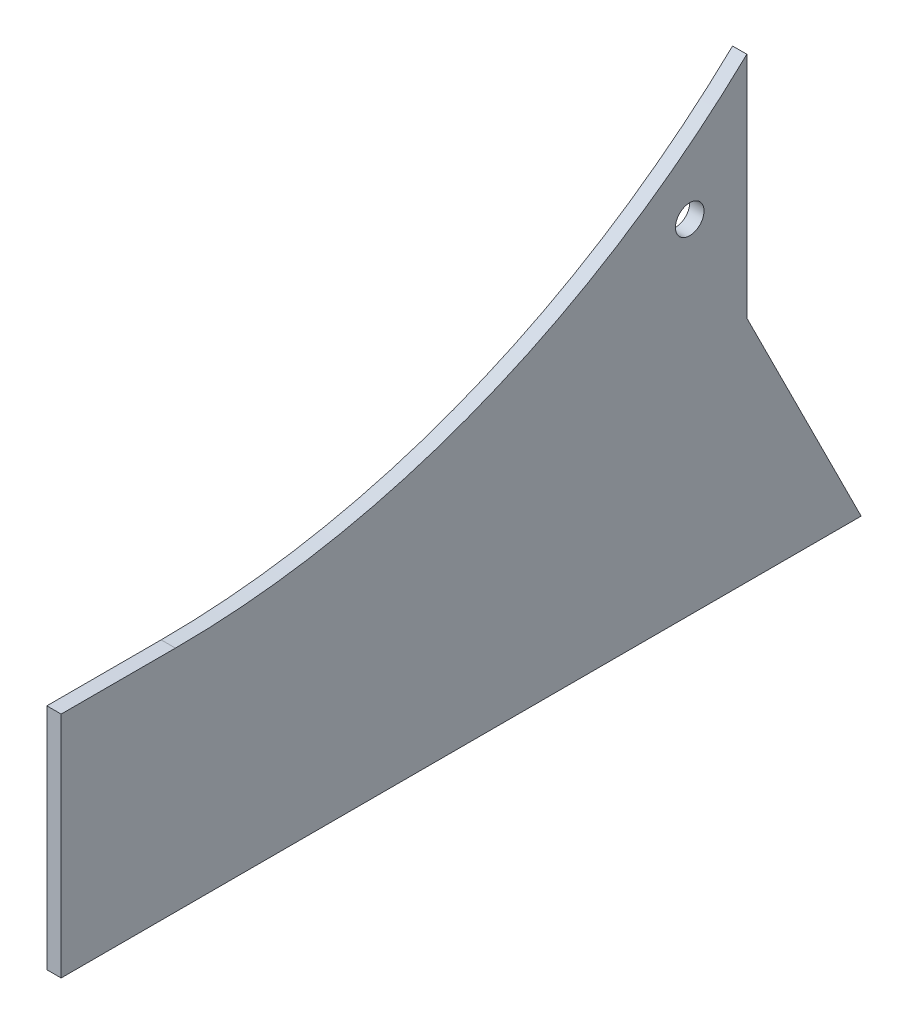
SolidWorks part; units mm, degrees
ref_plane "Front Plane" through (0, 0, 0) normal (0, 0, 1) x (1, 0, 0)
ref_plane "Top Plane" through (0, 0, 0) normal (0, 1, 0) x (1, 0, 0)
ref_plane "Right Plane" through (0, 0, 0) normal (1, 0, 0) x (0, 0, -1)
sketch "Sketch1" plane through (0, 0, 0) normal (1, 0, 0) x (0, 0, -1)
  line L0 (127, 50.8) -> (127, 152.4)
  line L1 (-177.8, -50.8) -> (177.8, -50.8)
  line L2 (-177.8, -50.8) -> (-177.8, 50.8)
  line L3 (-177.8, 50.8) -> (177.8, 50.8)
  line L4 (177.8, -50.8) -> (177.8, 50.8)
  line L5 (-177.8, -50.8) -> (177.8, 50.8) construction
  line L6 (-177.8, 50.8) -> (177.8, -50.8) construction
  line L7 (127, 152.4) -> (-127, 50.8)
  line L8 (127, 50.8) -> (177.8, -50.8)
  arc A0 (-127, 50.8) -> (127, 152.4) centre (-127, 419.1) ccw
  point P0 (0, 0)
  dimension "D1" = 101.6
  dimension "D2" = 355.6
  dimension "D3" = 101.6
  dimension "D4" = 50.8
  dimension "D5" = 50.8
extrude "Boss-Extrude1" add sketch "Sketch1" along normal blind 6.35 contours L1 L4 L3 L2 | A0 L3 L0 region at (0, 80.3936, -65.3852) region at (0, -1.3026, 12.3744)
sketch "Sketch2" plane through (6.35, 0, 0) normal (1, 0, 0) x (0, 0, -1)
  line L0 (127, 50.8) -> (127, 152.4) construction
  line L3 (-177.8, 50.8) -> (-127, 50.8) construction
  circle A0 centre (101.6, 101.6) radius 6.35
  dimension "D1" = 12.7
  dimension "D2" = 25.4
  dimension "D3" = 50.8
extrude "Cut-Extrude1" cut sketch "Sketch2" against normal blind 6.35
